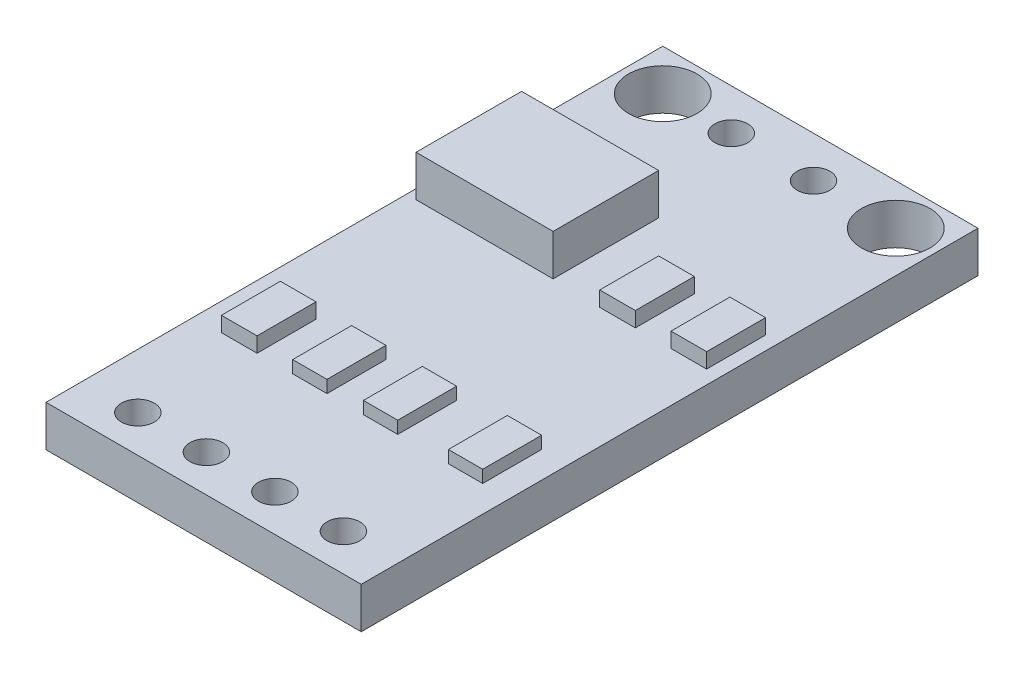
SolidWorks part; units mm, degrees
material "Copper"
ref_plane "Front Plane" through (0, 0, 0) normal (0, 0, 1) x (1, 0, 0)
ref_plane "Top Plane" through (0, 0, 0) normal (0, 1, 0) x (1, 0, 0)
ref_plane "Right Plane" through (0, 0, 0) normal (1, 0, 0) x (0, 0, -1)
sketch "Sketch1" plane through (0, 0, 0) normal (0, 1, 0) x (1, 0, 0)
  line L1 (-5.75, -11.25) -> (5.75, -11.25)
  line L2 (-5.75, -11.25) -> (-5.75, 11.25)
  line L3 (-5.75, 11.25) -> (5.75, 11.25)
  line L4 (5.75, -11.25) -> (5.75, 11.25)
  line L5 (0, 11.25) -> (0, -11.25) construction
  line L6 (-5.75, 0) -> (5.75, 0) construction
  point P0 (0, 0)
  dimension "D1" = 22.5
  dimension "D2" = 11.5
extrude "PCB" add sketch "Sketch1" along normal blind 1.5
sketch "Sketch2" plane through (0, 1.5, 0) normal (0, 1, 0) x (1, 0, 0)
  line L0 (-5.75, 11.25) -> (-5.75, -11.25) construction
  line L1 (5.75, 11.25) -> (-5.75, 11.25) construction
  line L2 (-5.75, -11.25) -> (5.75, -11.25) construction
  line L3 (5.75, -11.25) -> (5.75, 11.25) construction
  line L4 (4.25, 9.75) -> (4.25, 11.25) construction
  line L5 (4.25, 9.75) -> (5.75, 9.75) construction
  line L6 (-4.25, 9.75) -> (-4.25, 11.25) construction
  line L7 (-4.25, 9.75) -> (-5.75, 9.75) construction
  circle A0 centre (-1.75, 9.75) radius 0.6
  circle A1 centre (-3.75, -9.9) radius 0.6
  circle A2 centre (-4.25, 9.75) radius 1.25
  circle A3 centre (4.25, 9.75) radius 1.25
  dimension "D4" = 1.2
  dimension "D7" = 2.5
  dimension "D2" = 4
  dimension "D3" = 1.5
  dimension "D5" = 2
  dimension "D6" = 1.35
  dimension "D11" = 1.5
extrude "Initial Input Holes" cut sketch "Sketch2<4>" against normal through all contours A1 region at (-3.75, 1.5, 9.9)
sketch "Sketch2<4>" plane through (0, 1.5, 0) normal (0, 1, 0) x (1, 0, 0) same geometry as "Sketch2"
pattern_linear "Input Holes LPattern" count 4 spacing 2.5 along (1, 0, 0) of "Initial Input Holes"
extrude "Initial Output Hole" cut sketch "Sketch2<3>" against normal through all contours A0
sketch "Sketch2<3>" plane through (0, 1.5, 0) normal (0, 1, 0) x (1, 0, 0) same geometry as "Sketch2"
pattern_linear "Output Holes LPattern" count 2 spacing 3 along (1, 0, 0) of "Initial Output Hole"
extrude "Mounting Holes" cut sketch "Sketch2" against normal through all contours A2 | A3 region at (-4.25, 1.5, -9.75) region at (4.25, 1.5, -9.75)
sketch "Sketch3" plane through (0, 1.5, 0) normal (0, 1, 0) x (1, 0, 0)
  line L0 (-5.75, -11.25) -> (5.75, -11.25) construction
  line L1 (-5.4, 5.75) -> (-0.4, 5.75)
  line L2 (-5.4, 5.75) -> (-5.4, 1.9)
  line L3 (-5.4, 1.9) -> (-0.4, 1.9)
  line L4 (-0.4, 5.75) -> (-0.4, 1.9)
  line L5 (1.35, 4) -> (2.65, 4)
  line L6 (1.35, 4) -> (1.35, 1.85)
  line L7 (1.35, 1.85) -> (2.65, 1.85)
  line L8 (2.65, 4) -> (2.65, 1.85)
  line L9 (3.95, 4) -> (5.25, 4)
  line L10 (3.95, 4) -> (3.95, 1.85)
  line L11 (3.95, 1.85) -> (5.25, 1.85)
  line L12 (5.25, 4) -> (5.25, 1.85)
  line L13 (3.53, -3.7) -> (4.78, -3.7)
  line L14 (3.53, -3.7) -> (3.53, -5.85)
  line L15 (3.53, -5.85) -> (4.78, -5.85)
  line L16 (4.78, -3.7) -> (4.78, -5.85)
  line L17 (0.43, -3.7) -> (1.68, -3.7)
  line L18 (0.43, -3.7) -> (0.43, -5.85)
  line L19 (0.43, -5.85) -> (1.68, -5.85)
  line L20 (1.68, -3.7) -> (1.68, -5.85)
  line L21 (-2.15, -3.7) -> (-0.9, -3.7)
  line L22 (-2.15, -3.7) -> (-2.15, -5.85)
  line L23 (-2.15, -5.85) -> (-0.9, -5.85)
  line L24 (-0.9, -3.7) -> (-0.9, -5.85)
  line L25 (-4.75, -3.7) -> (-3.45, -3.7)
  line L26 (-4.75, -3.7) -> (-4.75, -5.85)
  line L27 (-4.75, -5.85) -> (-3.45, -5.85)
  line L28 (-3.45, -3.7) -> (-3.45, -5.85)
  line L29 (5.75, 11.25) -> (-5.75, 11.25) construction
  line L30 (-5.75, 11.25) -> (-5.75, -11.25) construction
  line L31 (5.75, -11.25) -> (5.75, 11.25) construction
  dimension "D1" = 1.3
  dimension "D2" = 2.15
  dimension "D3" = 1.25
  dimension "D4" = 2.15
  dimension "D5" = 5.4
  dimension "D6" = 5.4
  dimension "D7" = 5
  dimension "D8" = 3.85
  dimension "D9" = 5.5
  dimension "D10" = 7.25
  dimension "D11" = 1.3
  dimension "D12" = 1.85
  dimension "D13" = 1.33
  dimension "D14" = 1.3
  dimension "D15" = 1
  dimension "D16" = 0.5
  dimension "D17" = 0.35
extrude "Capacitors" add sketch "Sketch3<4>" along normal blind 0.55 contours L8 L5 L6 L7 | L12 L9 L10 L11 | L28 L25 L26 L27 region at (2, 1.5, -2.925) region at (4.6, 1.5, -2.925) region at (-4.1, 1.5, 4.775)
sketch "Sketch3<4>" plane through (0, 1.5, 0) normal (0, 1, 0) x (1, 0, 0) same geometry as "Sketch3"
extrude "Resistors" add sketch "Sketch3<3>" along normal blind 0.45 contours L24 L21 L22 L23 | L20 L17 L18 L19 | L16 L13 L14 L15 region at (4.155, 1.5, 4.775) region at (1.055, 1.5, 4.775) region at (-1.525, 1.5, 4.775)
sketch "Sketch3<3>" plane through (0, 1.5, 0) normal (0, 1, 0) x (1, 0, 0) same geometry as "Sketch3"
extrude "Transceiver Chip" add sketch "Sketch3" along normal blind 1.5 contours L4 L1 L2 L3 region at (-2.9, 1.5, -3.825)
